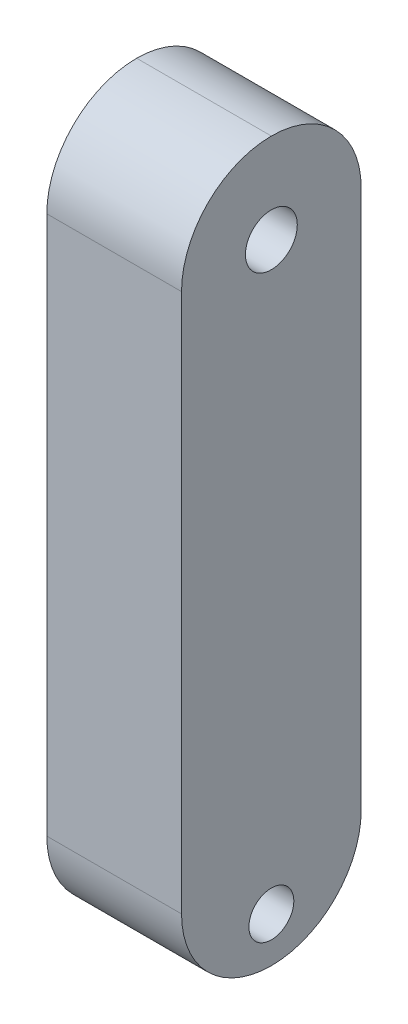
SolidWorks part; units mm, degrees
ref_plane "Front Plane" through (0, 0, 0) normal (0, 0, 1) x (1, 0, 0)
ref_plane "Top Plane" through (0, 0, 0) normal (0, 1, 0) x (1, 0, 0)
ref_plane "Right Plane" through (0, 0, 0) normal (1, 0, 0) x (0, 0, -1)
sketch "Sketch1" plane through (0, 0, 0) normal (0, 1, 0) x (1, 0, 0)
  line L1 (-19.05, -25.4) -> (19.05, -25.4)
  line L2 (-19.05, -25.4) -> (-19.05, 25.4)
  line L3 (-19.05, 25.4) -> (19.05, 25.4)
  line L4 (19.05, -25.4) -> (19.05, 25.4)
  line L5 (-19.05, -25.4) -> (19.05, 25.4) construction
  line L6 (-19.05, 25.4) -> (19.05, -25.4) construction
  point P0 (0, 0)
  dimension "D1" = 38.1
  dimension "D2" = 50.8
extrude "Boss-Extrude1" add sketch "Sketch1" along normal mid plane 203.2
sketch "Sketch2" plane through (19.05, 0, 0) normal (1, 0, 0) x (0, 0, -1)
  line L0 (-25.4, -101.6) -> (25.4, -101.6) construction
  circle A0 centre (0, -88.9) radius 6.35
  dimension "D1" = 12.7
  dimension "D2" = 12.7
extrude "Cut-Extrude1" cut sketch "Sketch2" against normal through all
fillet "Fillet1" radius 25.4 4 edges at (0, -101.6, -25.4) (0, -101.6, 25.4) (0, 101.6, 25.4) (0, 101.6, -25.4)
extrude "Cut-Extrude2" cut sketch "Sketch3" against normal through all
sketch "Sketch3" plane through (292.1, -73.4749, -233.0847) normal (1, 0, 0) x (0, 0.5719, -0.8203)
  circle A1 centre (-105.6027, 256.0842) radius 7.3323
